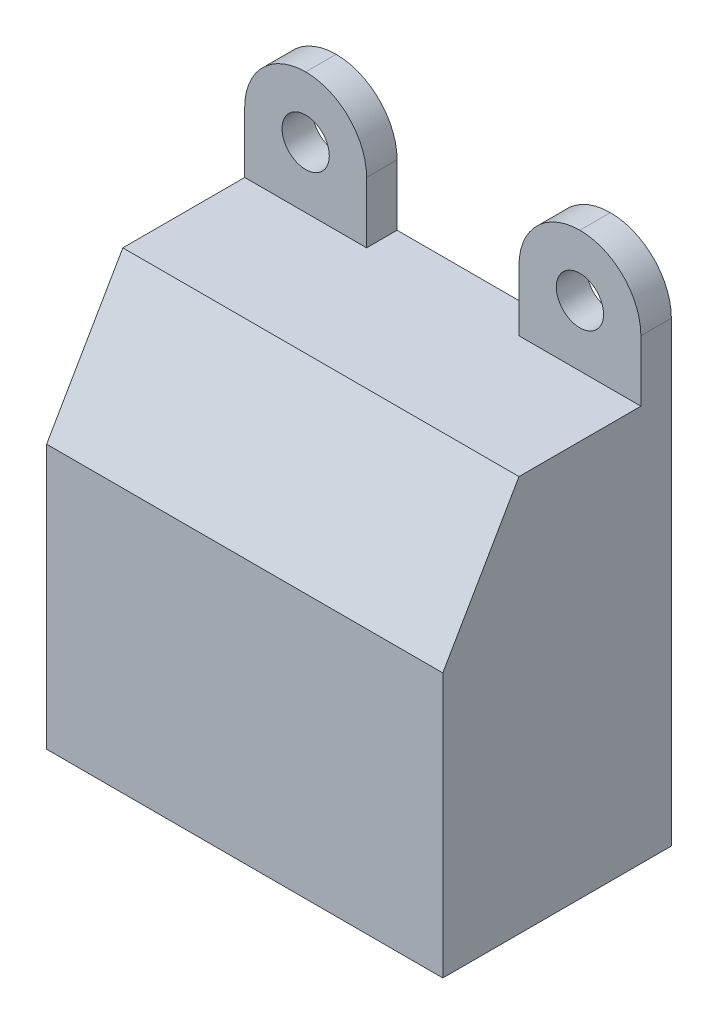
SolidWorks part; units mm, degrees
ref_plane "Front Plane" through (0, 0, 0) normal (0, 0, 1) x (1, 0, 0)
ref_plane "Top Plane" through (0, 0, 0) normal (0, 1, 0) x (1, 0, 0)
ref_plane "Right Plane" through (0, 0, 0) normal (1, 0, 0) x (0, 0, -1)
sketch "Sketch1" plane through (0, 0, 0) normal (0, 0, 1) x (1, 0, 0)
  line L0 (85, 68) -> (70, 68) construction
  line L1 (70, 0) -> (70, 136) construction
  line L2 (60, 0) -> (80, 0) construction
  line L3 (80, 136) -> (60, 136) construction
  line L5 (70, 0) -> (44, 0)
  line L6 (70, 0) -> (70, 26)
  line L7 (70, 26) -> (44, 26)
  line L8 (44, 0) -> (44, 26)
  dimension "D1" = 15
  dimension "D2" = 26
  dimension "D3" = 26
extrude "Boss-Extrude1" add sketch "Sketch1" along normal blind 15
chamfer "Chamfer1" distance 5 angle 60 1 edges at (57, 26, 15) first distance on face at (57, 26, 7.5)
sketch "Sketch2" plane through (0, 26, 0) normal (0, 1, 0) x (1, 0, 0)
  line L1 (44, 0) -> (52, 0)
  line L2 (44, 0) -> (44, -2)
  line L3 (44, -2) -> (52, -2)
  line L4 (52, 0) -> (52, -2)
  line L5 (70, 0) -> (62, 0)
  line L6 (70, 0) -> (70, -2)
  line L7 (70, -2) -> (62, -2)
  line L8 (62, 0) -> (62, -2)
  dimension "D1" = 2
  dimension "D2" = 8
  dimension "D3" = 8
extrude "Boss-Extrude2" add sketch "Sketch2" along normal blind 8
fillet "Fillet1" radius 4 4 edges at (44, 34, 1) (52, 34, 1) (62, 34, 1) (70, 34, 1)
sketch "Sketch5" plane through (0, 0, 2) normal (0, 0, 1) x (1, 0, 0)
  circle A0 centre (66, 30) radius 1.55
  circle A1 centre (48, 30) radius 1.55
  dimension "D1" = 3.1
  dimension "D2" = 3.1
extrude "Cut-Extrude2" cut sketch "Sketch5" against normal up to next
